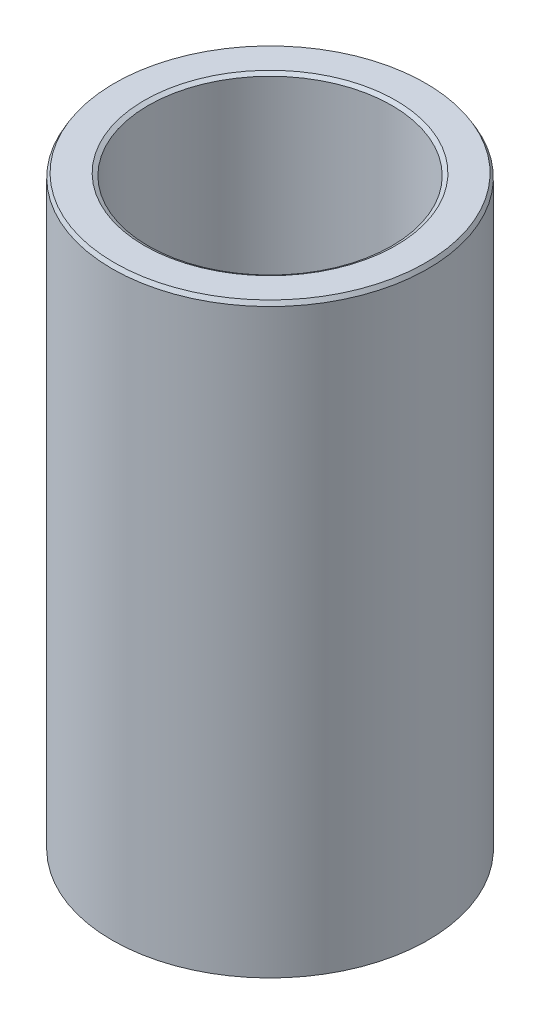
SolidWorks part; units mm, degrees
ref_plane "Front Plane" through (0, 0, 0) normal (0, 0, 1) x (1, 0, 0)
ref_plane "Top Plane" through (0, 0, 0) normal (0, 1, 0) x (1, 0, 0)
ref_plane "Right Plane" through (0, 0, 0) normal (1, 0, 0) x (0, 0, -1)
sketch "Sketch1" plane through (0, 0, 0) normal (0, 1, 0) x (1, 0, 0)
  circle A0 centre (0, 0) radius 57.5
  dimension "SLEEVE_OD" = 115
extrude "Boss-Extrude1" add sketch "Sketch1" along normal blind 214.0368
sketch "Sketch2" plane through (0, 0, 0) normal (0, 1, 0) x (1, 0, 0)
  circle A0 centre (0, 0) radius 44.3331
  dimension "BORE_D" = 88.6662
extrude "Cut-Extrude1" cut sketch "Sketch2" along normal through all
chamfer "Chamfer1" distance 1.4725 angle 30 4 edges at (0, 214.0368, 44.3331) (0, 0, 44.3331) (0, 0, 57.5) (0, 214.0368, 57.5) first distance on face at (0, 214.0368, 44.3331) first distance on face at (0, 0, 44.3331) first distance on face at (0, 214.0368, 57.5)
